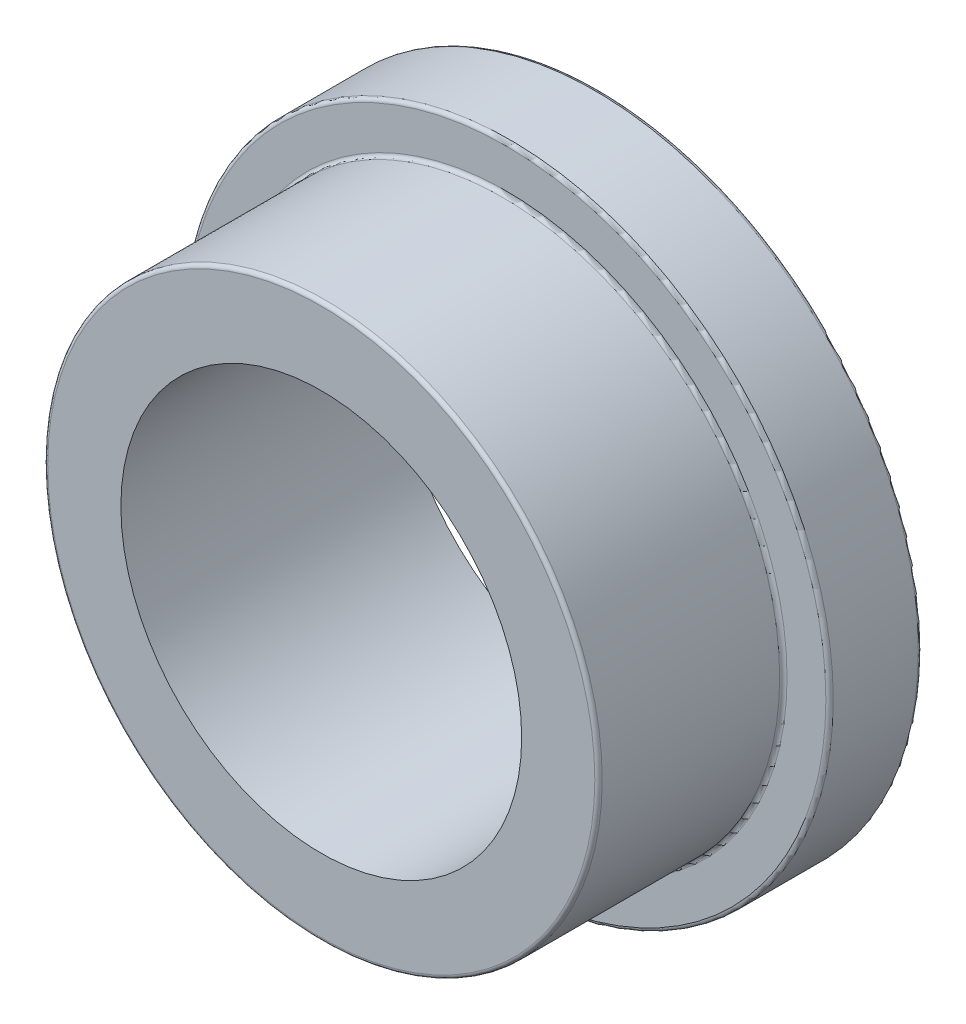
SolidWorks part; units mm, degrees
material "Nylon 101"
ref_plane "Front Plane" through (0, 0, 0) normal (0, 0, 1) x (1, 0, 0)
ref_plane "Top Plane" through (0, 0, 0) normal (0, 1, 0) x (1, 0, 0)
ref_plane "Right Plane" through (0, 0, 0) normal (1, 0, 0) x (0, 0, -1)
sketch "Sketch1" plane through (0, 0, 0) normal (0, 1, 0) x (1, 0, 0)
  line L0 (6.885, -6.35) -> (9.525, -6.35)
  line L1 (9.525, -6.35) -> (9.525, 0)
  line L2 (9.525, 0) -> (11.1125, 0)
  line L3 (11.1125, 0) -> (11.1125, 3.175)
  line L4 (11.1125, 3.175) -> (6.885, 3.175)
  line L5 (6.885, 3.175) -> (6.885, -6.35)
  line L6 (0, 3.175) -> (0, -6.35) construction
  dimension "D1" = 6.885
  dimension "D2" = 9.525
  dimension "D3" = 11.1125
  dimension "D4" = 6.35
  dimension "D5" = 9.525
revolve "Revolve1" add sketch "Sketch1" angle 360 about L6 reverse direction yes
fillet "Minor Fillet Smoothing" radius 0.127 4 edges at (9.525, 0, 0) (9.525, 0, 6.35) (11.1125, 0, 0) (11.1125, 0, -3.175)
